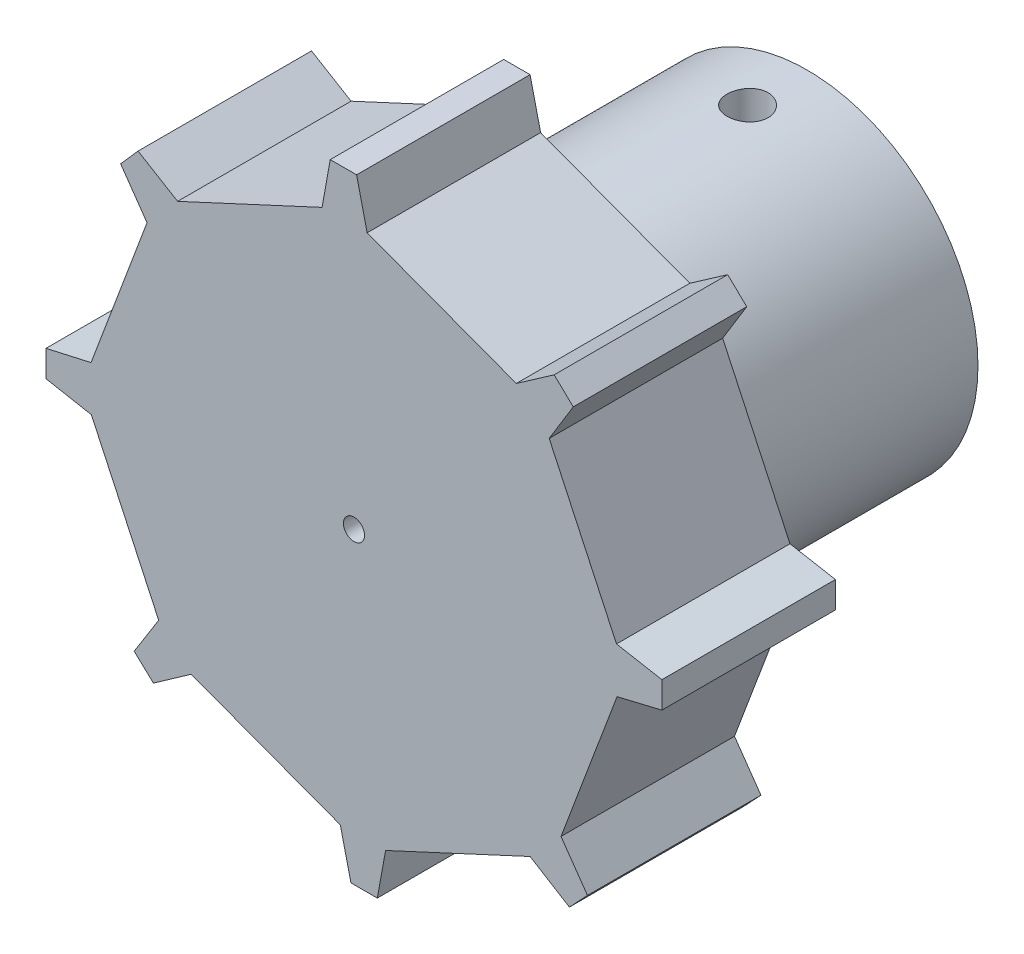
SolidWorks part; units mm, degrees
ref_plane "Front Plane" through (0, 0, 0) normal (0, 0, 1) x (1, 0, 0)
ref_plane "Top Plane" through (0, 0, 0) normal (0, 1, 0) x (1, 0, 0)
ref_plane "Right Plane" through (0, 0, 0) normal (1, 0, 0) x (0, 0, -1)
ref_plane "Plane1" through (0, 0, 0) normal (0, 0, -1) x (-1, 0, 0)
sketch "Sketch1" plane through (0, 0, 0) normal (0, 0, -1) x (-1, 0, 0)
  line L0 (22.5256, -1.7366) -> (22.5256, 0.1945)
  line L1 (22.5256, 0.1945) -> (19.2298, 0.9367)
  line L2 (19.2298, 0.9367) -> (15.1287, 11.8517)
  line L3 (15.1287, 11.8517) -> (17.0636, 14.621)
  line L4 (17.0636, 14.621) -> (15.7864, 16.0694)
  line L5 (15.7864, 16.0694) -> (12.8909, 14.3292)
  line L6 (12.8909, 14.3292) -> (2.313, 19.235)
  line L7 (2.313, 19.235) -> (1.7197, 22.5608)
  line L8 (1.7197, 22.5608) -> (-0.2115, 22.5608)
  line L9 (-0.2115, 22.5608) -> (-0.9837, 19.272)
  line L10 (-0.9837, 19.272) -> (-11.9025, 15.1806)
  line L11 (-11.9025, 15.1806) -> (-14.6739, 17.1124)
  line L12 (-14.6739, 17.1124) -> (-16.0731, 15.7814)
  line L13 (-16.0731, 15.7814) -> (-14.3088, 12.9004)
  line L14 (-14.3088, 12.9004) -> (-19.2369, 2.3329)
  line L15 (-19.2369, 2.3329) -> (-22.561, 1.7301)
  line L16 (-22.561, 1.7301) -> (-22.561, -0.201)
  line L17 (-22.561, -0.201) -> (-19.2755, -0.9874)
  line L18 (-19.2755, -0.9874) -> (-15.1744, -11.9025)
  line L19 (-15.1744, -11.9025) -> (-17.1122, -14.6697)
  line L20 (-17.1122, -14.6697) -> (-15.7881, -16.0755)
  line L21 (-15.7881, -16.0755) -> (-12.9108, -14.3052)
  line L22 (-12.9108, -14.3052) -> (-2.333, -19.211)
  line L23 (-2.333, -19.211) -> (-1.7277, -22.5347)
  line L24 (-1.7277, -22.5347) -> (0.2034, -22.5347)
  line L25 (0.2034, -22.5347) -> (0.9785, -19.2465)
  line L26 (0.9785, -19.2465) -> (11.8972, -15.1551)
  line L27 (11.8972, -15.1551) -> (14.6596, -17.0998)
  line L28 (14.6596, -17.0998) -> (16.0729, -15.7837)
  line L29 (16.0729, -15.7837) -> (14.2763, -12.9228)
  line L30 (14.2763, -12.9228) -> (19.2044, -2.3553)
  line L31 (19.2044, -2.3553) -> (22.5256, -1.7366)
extrude "Boss-Extrude1" add sketch "Sketch1" against normal blind 12.7
sketch "Sketch2" plane through (0, 0, 0) normal (0, 0, -1) x (-1, 0, 0)
  line L0 (7.602, 16.7821) -> (-7.6219, -16.7581) construction
  line L1 (12.8909, 14.3292) -> (2.313, 19.235) construction
  line L2 (-12.9108, -14.3052) -> (-2.333, -19.211) construction
  line L3 (16.7404, -7.639) -> (-16.7729, 7.6167) construction
  line L4 (14.2763, -12.9228) -> (19.2044, -2.3553) construction
  line L5 (-14.3088, 12.9004) -> (-19.2369, 2.3329) construction
  circle A0 centre (-0.0198, -0.0096) radius 0.775
  point P12 (-0.0198, -0.0096)
  dimension "D1" = 1.55
extrude "Cut-Extrude1" cut sketch "Sketch2" against normal up to next
ref_plane "Plane2" through (0, 4, 0) normal (0, 1, 0) x (1, 0, 0)
sketch "Sketch4" plane through (0, 0, 0) normal (0, 0, -1) x (-1, 0, 0)
  line L0 (0.7266, 2.6523) -> (-0.5675, 2.6908)
  line L32 (19.2044, -2.3553) -> (22.5256, -1.7366)
  line L33 (22.5256, -1.7366) -> (22.5256, 0.1945)
  line L34 (22.5256, 0.1945) -> (19.2298, 0.9367)
  line L35 (19.2298, 0.9367) -> (15.1287, 11.8517)
  line L36 (15.1287, 11.8517) -> (17.0636, 14.621)
  line L37 (17.0636, 14.621) -> (15.7864, 16.0694)
  line L38 (15.7864, 16.0694) -> (12.8909, 14.3292)
  line L39 (12.8909, 14.3292) -> (2.313, 19.235)
  line L40 (2.313, 19.235) -> (1.7197, 22.5608)
  line L41 (1.7197, 22.5608) -> (-0.2115, 22.5608)
  line L42 (-0.2115, 22.5608) -> (-0.9837, 19.272)
  line L43 (-0.9837, 19.272) -> (-11.9025, 15.1806)
  line L44 (-11.9025, 15.1806) -> (-14.6739, 17.1124)
  line L45 (-14.6739, 17.1124) -> (-16.0731, 15.7814)
  line L46 (-16.0731, 15.7814) -> (-14.3088, 12.9004)
  line L47 (-14.3088, 12.9004) -> (-19.2369, 2.3329)
  line L48 (-19.2369, 2.3329) -> (-22.561, 1.7301)
  line L49 (-22.561, 1.7301) -> (-22.561, -0.201)
  line L50 (-22.561, -0.201) -> (-19.2755, -0.9874)
  line L51 (-19.2755, -0.9874) -> (-15.1744, -11.9025)
  line L52 (-15.1744, -11.9025) -> (-17.1122, -14.6697)
  line L53 (-17.1122, -14.6697) -> (-15.7881, -16.0755)
  line L54 (-15.7881, -16.0755) -> (-12.9108, -14.3052)
  line L55 (-12.9108, -14.3052) -> (-2.333, -19.211)
  line L56 (-2.333, -19.211) -> (-1.7277, -22.5347)
  line L57 (-1.7277, -22.5347) -> (0.2034, -22.5347)
  line L58 (0.2034, -22.5347) -> (0.9785, -19.2465)
  line L59 (0.9785, -19.2465) -> (11.8972, -15.1551)
  line L60 (11.8972, -15.1551) -> (14.6596, -17.0998)
  line L61 (14.6596, -17.0998) -> (16.0729, -15.7837)
  line L62 (16.0729, -15.7837) -> (14.2763, -12.9228)
  line L63 (14.2763, -12.9228) -> (19.2044, -2.3553)
  line L64 (19.2044, -2.3553) -> (22.5256, -1.7366)
  line L65 (22.5256, -1.7366) -> (22.5256, 0.1945)
  line L66 (22.5256, 0.1945) -> (19.2298, 0.9367)
  line L67 (19.2298, 0.9367) -> (15.1287, 11.8517)
  line L68 (15.1287, 11.8517) -> (17.0636, 14.621)
  line L69 (17.0636, 14.621) -> (15.7864, 16.0694)
  line L70 (15.7864, 16.0694) -> (12.8909, 14.3292)
  line L71 (12.8909, 14.3292) -> (2.313, 19.235)
  line L72 (2.313, 19.235) -> (1.7197, 22.5608)
  line L73 (1.7197, 22.5608) -> (-0.2115, 22.5608)
  line L74 (-0.2115, 22.5608) -> (-0.9837, 19.272)
  line L75 (-0.9837, 19.272) -> (-11.9025, 15.1806)
  line L76 (-11.9025, 15.1806) -> (-14.6739, 17.1124)
  line L77 (-14.6739, 17.1124) -> (-16.0731, 15.7814)
  line L78 (-16.0731, 15.7814) -> (-14.3088, 12.9004)
  line L79 (-14.3088, 12.9004) -> (-19.2369, 2.3329)
  line L80 (-19.2369, 2.3329) -> (-22.561, 1.7301)
  line L81 (-22.561, 1.7301) -> (-22.561, -0.201)
  line L82 (-22.561, -0.201) -> (-19.2755, -0.9874)
  line L83 (-19.2755, -0.9874) -> (-15.1744, -11.9025)
  line L84 (-15.1744, -11.9025) -> (-17.1122, -14.6697)
  line L85 (-17.1122, -14.6697) -> (-15.7881, -16.0755)
  line L86 (-15.7881, -16.0755) -> (-12.9108, -14.3052)
  line L87 (-12.9108, -14.3052) -> (-2.333, -19.211)
  line L88 (-2.333, -19.211) -> (-1.7277, -22.5347)
  line L89 (-1.7277, -22.5347) -> (0.2034, -22.5347)
  line L90 (0.2034, -22.5347) -> (0.9785, -19.2465)
  line L91 (0.9785, -19.2465) -> (11.8972, -15.1551)
  line L92 (11.8972, -15.1551) -> (14.6596, -17.0998)
  line L93 (14.6596, -17.0998) -> (16.0729, -15.7837)
  line L94 (16.0729, -15.7837) -> (14.2763, -12.9228)
  line L95 (14.2763, -12.9228) -> (19.2044, -2.3553)
  circle A2 centre (0, 0) radius 12.5
  circle A3 centre (0, 0) radius 2.75
  dimension "D2" = 5.5
  dimension "D1" = 0
extrude "Boss-Extrude3" add sketch "Sketch4" along normal offset from surface (20.5 mm away) 0.5 contours A2 A3 region at (12.1464, 0, 0)
extrude "Boss-Extrude4" add sketch "Sketch4<4>" along normal up to surface (20.5 mm away) contours L0 A3 region at (-0.0805, 2.7025, 0) up to face at (-2.75, 0, -20.5)
sketch "Sketch4<4>" plane through (0, 0, 0) normal (0, 0, -1) x (-1, 0, 0) same geometry as "Sketch4"
sketch "Sketch5" plane through (0, 4, 0) normal (0, 1, 0) x (1, 0, 0)
  circle A0 centre (0, 16.1301) radius 1.5
  dimension "D1" = 3
extrude "Cut-Extrude2" cut sketch "Sketch5" along normal blind 12 and the other way blind 2 contours A0
sketch "Sketch6" plane through (0, 0, -20.5) normal (0, 0, -1) x (-1, 0, 0)
  line L0 (0.7266, 2.6523) -> (-0.5675, 2.6908) construction
  line L1 (4.5795, 7.5376) -> (-4.4205, 7.8055)
  line L3 (4.5795, 7.5376) -> (4.4617, 3.578)
  line L4 (4.4617, 3.578) -> (-4.5383, 3.846)
  line L5 (-4.5383, 3.846) -> (-4.4205, 7.8055)
  point P0 (0.0795, 2.6715)
  point P6 (0.0795, 7.6715)
  dimension "D2" = 9
  dimension "D1" = 5
extrude "Cut-Extrude3" cut sketch "Sketch6" against normal blind 17
